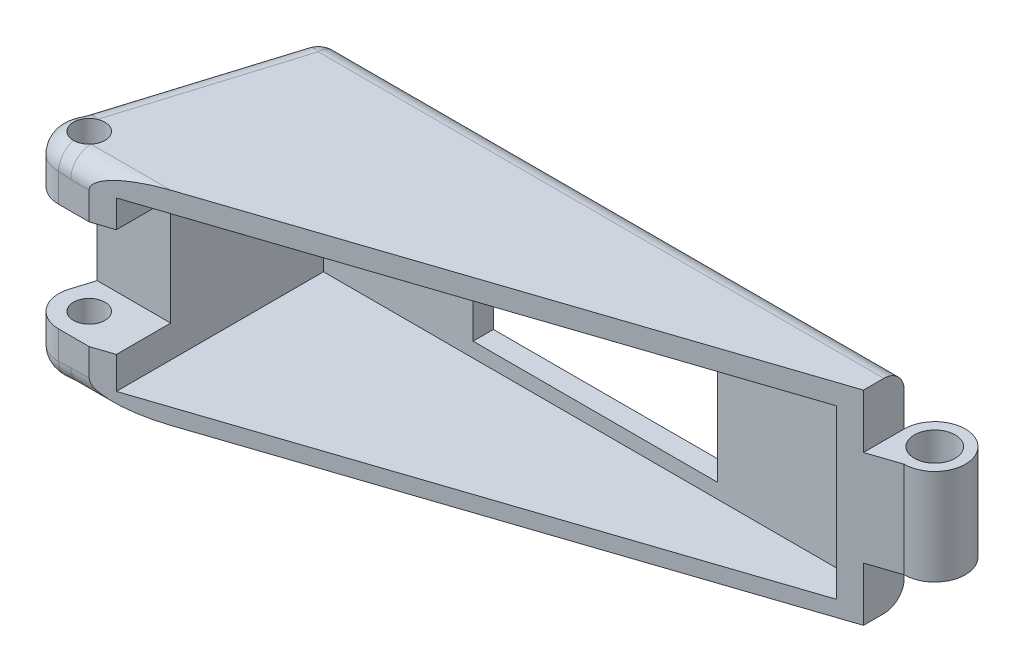
SolidWorks part; units mm, degrees
ref_plane "Front Plane" through (0, 0, 0) normal (0, 0, 1) x (1, 0, 0)
ref_plane "Top Plane" through (0, 0, 0) normal (0, 1, 0) x (1, 0, 0)
ref_plane "Right Plane" through (0, 0, 0) normal (1, 0, 0) x (0, 0, -1)
sketch "Sketch1" plane through (0, 0, 0) normal (0, 1, 0) x (1, 0, 0)
  line L0 (-13.3387, -5.7532) -> (16.6613, 4.2468)
  line L1 (-13.3387, -2.7532) -> (-13.3387, 5.7468)
  line L2 (-13.3387, 5.7468) -> (15.1613, 5.7468)
  line L3 (-14.8387, -5.7532) -> (-13.3387, -5.7532)
  line L4 (-14.8387, -2.7532) -> (-13.3387, -2.7532)
  circle A1 centre (-14.8387, -4.2532) radius 0.775
  arc A2 (-14.8387, -2.7532) -> (-14.8387, -5.7532) centre (-14.8387, -4.2532) ccw
  arc A3 (16.6613, 4.2468) -> (15.1613, 5.7468) centre (16.6613, 5.7468) ccw
  circle A4 centre (16.6613, 5.7468) radius 1
  dimension "D1" = 28.5
  dimension "D2" = 2
  dimension "D3" = 1.55
extrude "Boss-Extrude2" add sketch "Sketch1" along normal blind 10
sketch "Sketch2" plane through (0, 0, -5.7468) normal (0, 0, -1) x (-1, 0, 0)
  line L0 (-15.1613, 0) -> (-15.1613, 2.65) construction
  line L1 (-15.1613, 2.65) -> (-18.1613, 2.65) construction
  line L2 (-18.1613, 10) -> (-18.1613, 0) construction
  line L3 (-18.1613, 2.65) -> (-18.1613, 7.35) construction
  line L4 (-18.1613, 7.35) -> (-15.1613, 7.35) construction
  line L5 (-15.1613, 10) -> (-15.1613, 0) construction
  line L6 (-15.1613, 7.35) -> (-15.1613, 2.65) construction
  line L8 (-18.1613, 2.65) -> (-15.1613, 2.65)
  line L9 (-18.1613, 2.65) -> (-18.1613, 0)
  line L10 (-18.1613, 0) -> (-15.1613, 0)
  line L11 (-15.1613, 2.65) -> (-15.1613, 0)
  line L12 (-18.1613, 10) -> (-15.1613, 10)
  line L13 (-18.1613, 10) -> (-18.1613, 7.35)
  line L14 (-18.1613, 7.35) -> (-15.1613, 7.35)
  line L15 (-15.1613, 10) -> (-15.1613, 7.35)
  dimension "D1" = 2.65
  dimension "D2" = 4.7
  dimension "D3" = 2.65
extrude "Cut-Extrude3" cut sketch "Sketch2" against normal mid plane 10 contours L13 L12 L15 L14 | L9 L8 L11 L10
sketch "Sketch3" plane through (-13.3387, 0, 0) normal (-1, 0, 0) x (0, 0, 1)
  line L0 (2.7532, 10) -> (2.7532, 0) construction
  line L1 (2.7532, 7.65) -> (5.7532, 7.65)
  line L2 (2.7532, 7.65) -> (2.7532, 2.35)
  line L3 (2.7532, 2.35) -> (5.7532, 2.35)
  line L4 (5.7532, 7.65) -> (5.7532, 2.35)
  line L5 (5.7532, 10) -> (5.7532, 0) construction
  line L7 (2.7532, 0) -> (5.7532, 0) construction
  line L8 (5.7532, 10) -> (2.7532, 10) construction
  point P10 (0, 0)
  dimension "D1" = 2.35
  dimension "D2" = 5.3
  dimension "D3" = 2.35
extrude "Cut-Extrude4" cut sketch "Sketch3" along normal mid plane 10
sketch "Sketch4" plane through (0, 10, 0) normal (0, 1, 0) x (1, 0, 0)
  line L0 (-16.2727, -3.8131) -> (-13.3387, -2.7532)
  line L1 (-13.3387, 5.7468) -> (-16.2727, -3.8131)
  line L2 (-13.3387, -2.7532) -> (-13.3387, 5.7468)
  arc A1 (-14.8387, -2.7532) -> (-14.8387, -5.7532) centre (-14.8387, -4.2532) ccw construction
extrude "Boss-Extrude3" add sketch "Sketch4" against normal blind 2.35
ref_plane "Plane1" through (0, 5, 0) normal (0, 1, 0) x (1, 0, 0)
mirror "Mirror1" about plane through (0, 5, 0) normal (0, 1, 0) of "Boss-Extrude3"
sketch "Sketch5" plane through (-13.3387, 0, 0) normal (-1, 0, 0) x (0, 0, 1)
  line L0 (5.7532, 7.1419) -> (2.7532, 7.1419)
  line L1 (5.7532, 2.35) -> (5.7532, 7.65) construction
  line L2 (-5.7468, 2.35) -> (3.8131, 2.35) construction
  line L3 (-5.7468, 7.65) -> (2.7532, 7.65)
  line L4 (-5.7468, 7.65) -> (-5.7468, 2.35)
  line L5 (-5.7468, 2.35) -> (2.7532, 2.35)
  line L6 (2.7532, 7.65) -> (2.7532, 2.35)
  dimension "D1" = 3
extrude "Boss-Extrude4" add sketch "Sketch5" along normal up to surface (2.6087 mm away)
ref_plane "Plane2" through (0, 0, 10) normal (0, 0, 1) x (1, 0, 0)
sketch "Sketch8" plane through (0, 0, 10) normal (0, 0, 1) x (1, 0, 0)
  line L0 (-12.3387, 9) -> (-12.3387, 0.7786)
  line L1 (-13.3387, 10) -> (-13.3387, 7.65) construction
  line L2 (-13.3387, 10) -> (15.1613, 10) construction
  line L3 (-12.3387, 9) -> (14.1613, 9)
  line L4 (14.1613, 9) -> (14.1613, 0.7786)
  line L5 (14.1613, 0.7786) -> (-12.3387, 0.7786)
  line L6 (15.1613, 10) -> (15.1613, 7.35) construction
  dimension "D1" = 1
  dimension "D2" = 1
  dimension "D3" = 1
extrude "Cut-Extrude5" cut sketch "Sketch8" against normal offset from surface (14.7468 mm away) 1 up to face at (5.6613, 5, -5.7468)
sketch "Sketch9" plane through (0, 0, -5.7468) normal (0, 0, -1) x (-1, 0, 0)
  line L0 (-1, 1.5) -> (-1, 8.5) construction
  line L1 (-7, 8.5) -> (5, 8.5)
  line L2 (-7, 8.5) -> (-7, 1.5)
  line L3 (-7, 1.5) -> (5, 1.5)
  line L4 (5, 8.5) -> (5, 1.5)
  line L5 (-15.1613, 7.35) -> (-15.1613, 2.65) construction
  point P8 (-15.1613, 5)
  point P9 (-7, 5)
  dimension "D1" = 1
  dimension "D2" = 12
  dimension "D3" = 7
extrude "Cut-Extrude6" cut sketch "Sketch9" against normal blind 1
fillet "Fillet1" radius 1 9 edges at (-14.0887, 0, 5.7532) (-16.045, 10, 5.1447) (-14.8057, 10, -0.9669) (-16.045, 0, 5.1447) (-14.8057, 0, -0.9669) (-13.3387, 5, -5.7468) (0.9113, 10, -5.7468) (-14.0887, 10, 5.7532) (0.9113, 0, -5.7468)
